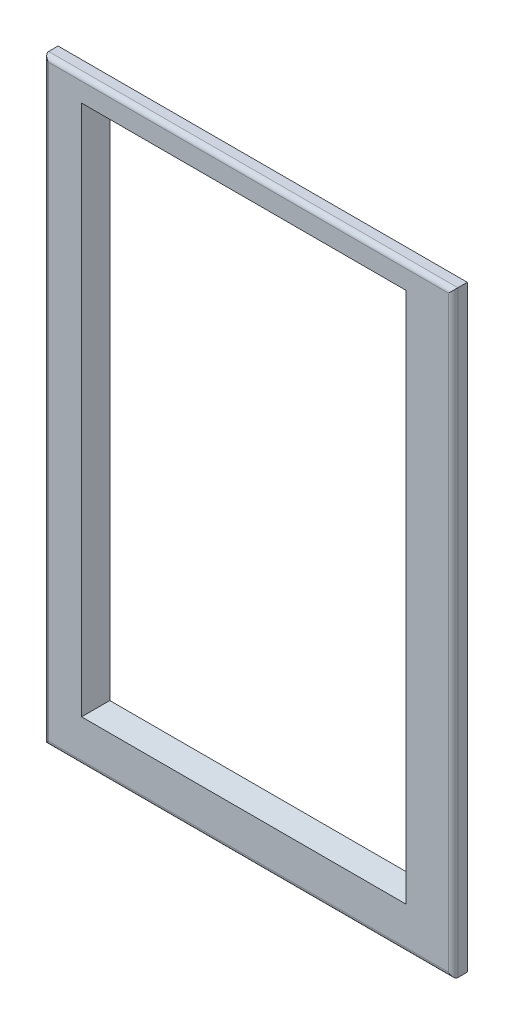
SolidWorks part; units mm, degrees
ref_plane "Front Plane" through (0, 0, 0) normal (0, 0, 1) x (1, 0, 0)
ref_plane "Top Plane" through (0, 0, 0) normal (0, 1, 0) x (1, 0, 0)
ref_plane "Right Plane" through (0, 0, 0) normal (1, 0, 0) x (0, 0, -1)
sketch "Sketch1" plane through (0, 0, 0) normal (0, 0, 1) x (1, 0, 0)
  line L0 (148.0903, -170.9986) -> (235.0903, -170.9986)
  line L1 (152.0903, -174.9986) -> (231.0903, -174.9986)
  line L2 (152.0903, -174.9986) -> (152.0903, -293.9986)
  line L3 (152.0903, -293.9986) -> (231.0903, -293.9986)
  line L4 (231.0903, -174.9986) -> (231.0903, -293.9986)
  line L5 (159.0903, -178.9986) -> (222.0903, -178.9986)
  line L6 (159.0903, -178.9986) -> (159.0903, -285.9986)
  line L7 (159.0903, -285.9986) -> (222.0903, -285.9986)
  line L8 (222.0903, -178.9986) -> (222.0903, -285.9986)
  line L9 (235.0903, -170.9986) -> (235.0903, -297.9986)
  line L10 (148.0903, -297.9986) -> (235.0903, -297.9986)
  line L11 (148.0903, -170.9986) -> (148.0903, -297.9986)
  dimension "D1" = 79
  dimension "D2" = 119
  dimension "D3" = 9
  dimension "D4" = 4
  dimension "D5" = 7
  dimension "D6" = 8
  dimension "D7" = 4
extrude "Boss-Extrude1" add sketch "Sketch1" along normal blind 3 contours L4 L1 L2 L3 L5 L8 L7 L6 | L0 L11 L10 L9 L1 L4 L3 L2 region at (191.5903, -172.538, 0) region at (191.5903, -176.4269, 0)
chamfer "Chamfer2" distance 3 angle 45 4 edges at (190.5903, -285.9986, 3) (159.0903, -232.4986, 3) (190.5903, -178.9986, 3) (222.0903, -232.4986, 3)
fillet "Fillet1" radius 1 4 edges at (191.5903, -297.9986, 3) (235.0903, -234.4986, 3) (191.5903, -170.9986, 3) (148.0903, -234.4986, 3)
